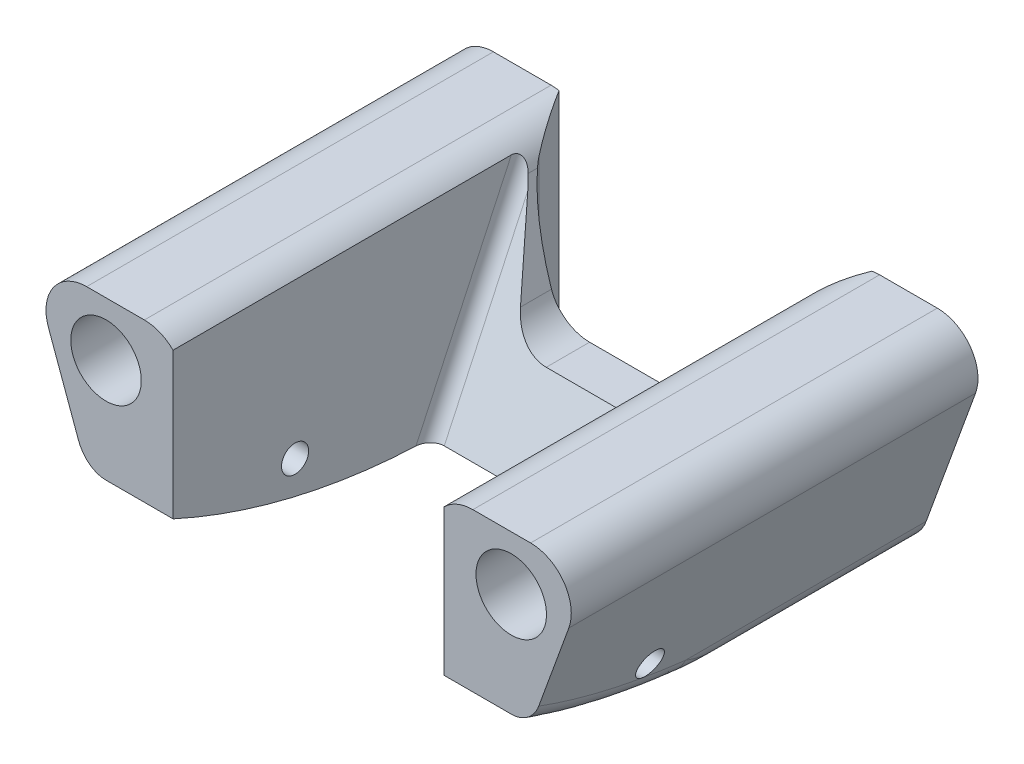
SolidWorks part; units mm, degrees
ref_plane "Front Plane" through (0, 0, 0) normal (0, 0, 1) x (1, 0, 0)
ref_plane "Top Plane" through (0, 0, 0) normal (0, 1, 0) x (1, 0, 0)
ref_plane "Right Plane" through (0, 0, 0) normal (1, 0, 0) x (0, 0, -1)
sketch "Sketch1" plane through (0, 0, 0) normal (0, 0, 1) x (1, 0, 0)
  line L0 (-19.1913, -37.0261) -> (-15.5516, -47.0261)
  line L1 (-12.7325, -49) -> (12.7325, -49)
  line L2 (15.5516, -47.0261) -> (19.1913, -37.0261)
  line L3 (-16.3722, -33) -> (-12.1155, -33)
  line L4 (-9.2964, -34.9739) -> (-7.0937, -41.0261)
  line L5 (-4.2746, -43) -> (4.2746, -43)
  line L6 (7.0937, -41.0261) -> (9.2964, -34.9739)
  line L7 (12.1155, -33) -> (16.3722, -33)
  circle A1 centre (-14.9441, -37) radius 2.6
  circle A3 centre (14.9441, -37) radius 2.6
  arc A4 (12.7325, -49) -> (15.5516, -47.0261) centre (12.7325, -46) ccw
  arc A5 (-15.5516, -47.0261) -> (-12.7325, -49) centre (-12.7325, -46) ccw
  arc A6 (19.1913, -37.0261) -> (16.3722, -33) centre (16.3722, -36) ccw
  arc A7 (-19.1913, -37.0261) -> (-16.3722, -33) centre (-16.3722, -36) cw
  arc A8 (-9.2964, -34.9739) -> (-12.1155, -33) centre (-12.1155, -36) ccw
  arc A9 (12.1155, -33) -> (9.2964, -34.9739) centre (12.1155, -36) ccw
  arc A10 (4.2746, -43) -> (7.0937, -41.0261) centre (4.2746, -40) ccw
  arc A11 (-7.0937, -41.0261) -> (-4.2746, -43) centre (-4.2746, -40) ccw
  dimension "D1" = 4
  dimension "D2" = 4
  dimension "D3" = 12
  dimension "D10" = 3
  dimension "D4" = 110
  dimension "D5" = 110
  dimension "D6" = 4
  dimension "D7" = 10
  dimension "D8" = 10
  dimension "D9" = 6
extrude "Boss-Extrude1" add sketch "Sketch1" along normal up to surface (35 mm away)
sketch "Sketch4" plane through (0, 0, 0) normal (1, 0, 0) x (0, 0, -1)
  line L0 (-35, -33) -> (0, -33) construction
  line L1 (-35, -49) -> (-11, -49)
  line L2 (-35, -49) -> (-35, -33)
  line L3 (-35, -33) -> (-3.5391, -33)
  line L5 (-11, -49) -> (-3.5391, -33)
extrude "Cut-Extrude3" cut sketch "Sketch4" against normal mid plane 20
sketch "Sketch5" plane through (10, 0, 0) normal (-1, 0, 0) x (0, 0, 1)
  circle A0 centre (21, -45.3) radius 1 construction
  circle A1 centre (21, -45.3) radius 1
extrude "Cut-Extrude4" cut sketch "Sketch5" against normal through all both and the other way through all
sketch "Sketch6" plane through (0, -49, 0) normal (0, -1, 0) x (1, 0, 0)
  line L0 (-12.7325, 0) -> (12.7325, 0) construction
  line L1 (-11.5325, 0) -> (11.5325, 0)
  line L3 (-8.6458, 5) -> (8.6458, 5)
  line L7 (-11.5325, 0) -> (-8.6458, 5)
  line L8 (11.5325, 0) -> (8.6458, 5)
  dimension "D4" = 60
  dimension "D5" = 60
extrude "Cut-Extrude5" cut sketch "Sketch6" against normal through all
fillet "Fillet1" radius 3 2 edges at (-8.6458, -42.8808, 5) (8.6458, -42.8808, 5)
sketch "Sketch7" plane through (10, 0, 0) normal (-1, 0, 0) x (0, 0, 1)
  line L0 (38, -42) -> (35, -42) construction
  line L1 (38, -42) -> (35, -42) construction
  line L3 (35, -49) -> (0, -49) construction
  line L4 (10, -49) -> (0, -49) construction
  line L5 (35, -47.0261) -> (35, -37.0261) construction
  line L6 (35, -42) -> (35, -49)
  line L7 (35, -49) -> (10, -49)
  arc A0 (35, -42) -> (10, -49) centre (10, -0.8571) cw
  dimension "D1" = 25
extrude "Cut-Extrude6" cut sketch "Sketch7" against normal through all both and the other way through all
fillet "Fillet2" radius 1 2 edges at (-10, -41.4313, 7.4707) (10, -41.4313, 7.4707)
fillet "Fillet3" radius 2 4 edges at (-14.5903, -48.3556, 17.8508) (14.5903, -48.3556, 17.8508) (-16.3325, -44.8807, 29.4849) (16.3325, -44.8807, 29.4849)
sketch "Sketch8" plane through (0, 0, 35) normal (0, 0, 1) x (1, 0, 0)
  line L1 (23.6351, -29.4856) -> (-25.3875, -29.4856)
  line L2 (23.6351, -29.4856) -> (23.6351, -50.4363)
  line L3 (23.6351, -50.4363) -> (-25.3875, -50.4363)
  line L4 (-25.3875, -29.4856) -> (-25.3875, -50.4363)
extrude "Cut-Extrude7" cut sketch "Sketch8" against normal blind 5
